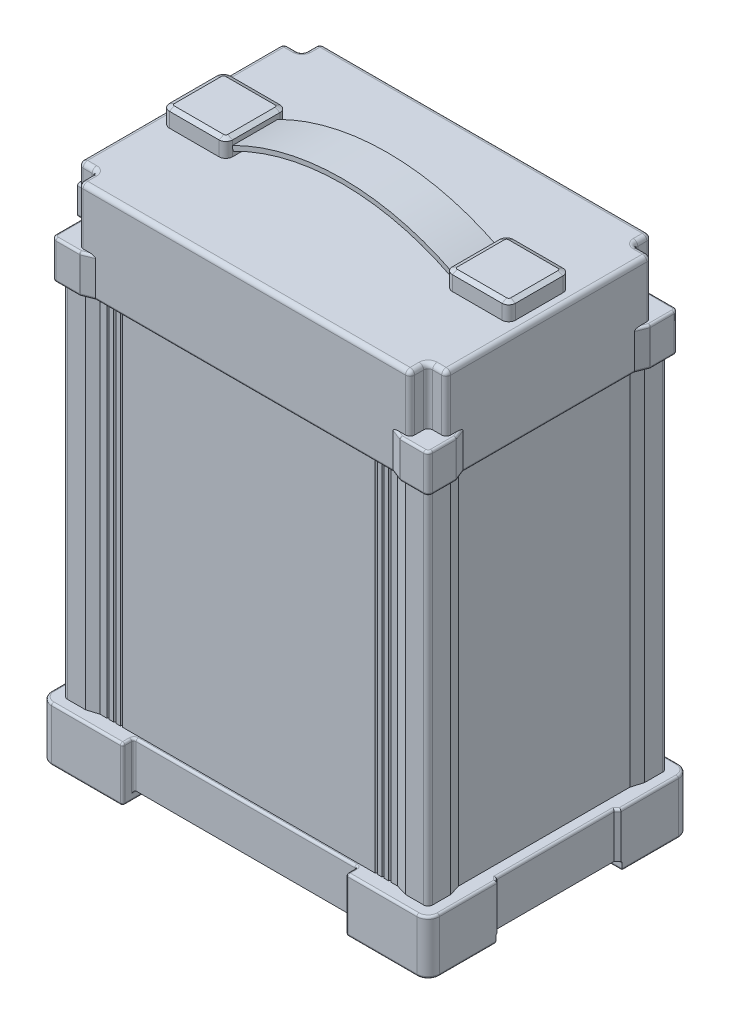
SolidWorks part; units mm, degrees
ref_plane "Front Plane" through (0, 0, 0) normal (0, 0, 1) x (1, 0, 0)
ref_plane "Top Plane" through (0, 0, 0) normal (0, 1, 0) x (1, 0, 0)
ref_plane "Right Plane" through (0, 0, 0) normal (1, 0, 0) x (0, 0, -1)
sketch "Sketch1" plane through (0, 0, 0) normal (0, 1, 0) x (1, 0, 0)
  line L0 (-81, 43) -> (-79.5, 38)
  line L1 (-81, -53) -> (-71, -53)
  line L2 (-81, -53) -> (-81, -43)
  line L3 (-81, 53) -> (-71, 53)
  line L4 (81, -53) -> (81, -43)
  line L6 (-79.5, 38) -> (-79.5, -38)
  line L7 (-66, -51.5) -> (66, -51.5)
  line L8 (79.5, 38) -> (79.5, -38)
  line L9 (-71, 53) -> (-66, 51.5)
  line L10 (-81, -43) -> (-79.5, -38)
  line L11 (-71, -53) -> (-66, -51.5)
  line L12 (66, 51.5) -> (71, 53)
  line L13 (81, 43) -> (79.5, 38)
  line L14 (81, -43) -> (79.5, -38)
  line L15 (71, -53) -> (66, -51.5)
  line L16 (71, 53) -> (81, 53)
  line L17 (71, -53) -> (81, -53)
  line L18 (81, 43) -> (81, 53)
  line L19 (-81, 43) -> (-81, 53)
  line L22 (-66, 51.5) -> (66, 51.5)
  line L23 (-79.5, 0) -> (79.5, 0) construction
  line L24 (0, 51.5) -> (0, -51.5) construction
  point P34 (0, 0)
  point P35 (0, 0)
  dimension "D1" = 162
  dimension "D2" = 106
  dimension "D5" = 10
  dimension "D6" = 5
  dimension "D7" = 10
  dimension "D8" = 1.5
  dimension "D4" = 10
  dimension "D9" = 10
  dimension "D3" = 1.5
extrude "Boss-Extrude1" add sketch "Sketch1" along normal blind 178
sketch "Sketch5" plane through (0, 0, 0) normal (0, -1, 0) x (1, 0, 0)
  line L0 (-66, 51.5) -> (66, 51.5) construction
  line L1 (0, 0) -> (0, 50000) construction
  line L2 (0, 0) -> (50000, 0) construction
  circle A0 centre (-62.5, 51.5) radius 0.5
  circle A1 centre (-59.5, 51.5) radius 0.5
  circle A2 centre (-56.5, 51.5) radius 0.5
  circle A3 centre (56.5, 51.5) radius 0.5
  circle A4 centre (59.5, 51.5) radius 0.5
  circle A5 centre (62.5, 51.5) radius 0.5
  circle A6 centre (62.5, -51.5) radius 0.5
  circle A7 centre (59.5, -51.5) radius 0.5
  circle A8 centre (56.5, -51.5) radius 0.5
  circle A9 centre (-56.5, -51.5) radius 0.5
  circle A10 centre (-59.5, -51.5) radius 0.5
  circle A11 centre (-62.5, -51.5) radius 0.5
  dimension "D1" = 1
  dimension "D2" = 3
  dimension "D3" = 3
  dimension "D4" = 3.5
extrude "Cut-Extrude1" cut sketch "Sketch5" against normal through all
fillet "Fillet1" radius 2 4 edges at (-81, 89, 53) (81, 89, 53) (-81, 89, -53) (81, 89, -53)
sketch "Sketch3" plane through (0, 0, 0) normal (0, 1, 0) x (1, 0, 0)
  line L1 (-86, 58) -> (-49.5, 58)
  line L2 (-86, 58) -> (-86, 28)
  line L3 (-86, -58) -> (-49.5, -58)
  line L4 (-49.5, 58) -> (-49.5, -58)
  line L5 (0, 0) -> (0, 89.5421) construction
  line L7 (-86, 28) -> (-84.5, 28)
  line L9 (-86, -28) -> (-84.5, -28)
  line L10 (-84.5, 28) -> (-84.5, -28)
  line L11 (-86, -28) -> (-86, -58)
  line L12 (86, 58) -> (86, 28)
  line L13 (-49.5, 53) -> (49.5, 53)
  line L14 (-49.5, 53) -> (-49.5, -53)
  line L15 (-49.5, -53) -> (49.5, -53)
  line L16 (49.5, 53) -> (49.5, -53)
  line L17 (86, 58) -> (49.5, 58)
  line L18 (49.5, 58) -> (49.5, -58)
  line L19 (86, -58) -> (49.5, -58)
  line L20 (86, -28) -> (86, -58)
  line L21 (86, -28) -> (84.5, -28)
  line L22 (84.5, 28) -> (84.5, -28)
  line L23 (86, 28) -> (84.5, 28)
  line L24 (66, 51.5) -> (63, 51.5) construction
  line L25 (-71, 53) -> (-79, 53) construction
  line L26 (-81, 51) -> (-81, 43) construction
  point P4 (-49.5, 0)
  point P14 (-84.5, 0)
  point P20 (49.5, 0)
  point P21 (0, 53)
  dimension "D3" = 1.5
  dimension "D4" = 30
  dimension "D5" = 1.5
  dimension "D1" = 5
  dimension "D2" = 5
  dimension "D6" = 99
extrude "Boss-Extrude2" add sketch "Sketch3" along normal blind 18 and the other way blind 2 separate body contours L9 L11 L3 L4 L1 L2 L7 L10 | L15 L5 L13 L4 | L5 L15 L16 L13 | L23 L12 L17 L18 L16 L19 L20 L21 L22 region at (-67.3958, 0, 0) region at (-24.75, 0, -51.5496) region at (67.3958, 0, 0)
sketch "Sketch4" plane through (0, -2, 0) normal (0, -1, 0) x (1, 0, 0)
  line L0 (-86, -28) -> (-84.5, -28) construction
  line L1 (-86, 58) -> (-49.5, 58)
  line L2 (-86, 58) -> (-86, 28)
  line L3 (-86, 28) -> (-49.5, 28)
  line L4 (-49.5, 58) -> (-49.5, 28)
  line L5 (-86, -58) -> (-49.5, -58)
  line L6 (-86, -58) -> (-86, -28)
  line L7 (-86, -28) -> (-49.5, -28)
  line L8 (-49.5, -58) -> (-49.5, -28)
  line L9 (86, 58) -> (49.5, 58) construction
  line L10 (86, -58) -> (49.5, -58)
  line L11 (86, -58) -> (86, -28)
  line L12 (86, -28) -> (49.5, -28)
  line L13 (49.5, -58) -> (49.5, -28)
  line L14 (86, 58) -> (49.5, 58)
  line L15 (86, 58) -> (86, 28)
  line L16 (86, 28) -> (49.5, 28)
  line L17 (49.5, 58) -> (49.5, 28)
extrude "Boss-Extrude3" add sketch "Sketch4" along normal blind 4
chamfer "Chamfer1" distance 2 angle 45 4 edges at (-84.5, 8, -28) (-84.5, 8, 28) (84.5, 8, 28) (84.5, 8, -28)
fillet "Fillet2" radius 1 56 edges at (67.75, -6, 28) (49.5, -6, 43) (67.75, -6, 58) (86, -6, 43) (-67.75, -6, 58) (-49.5, -6, 43) (-67.75, -6, 28) (-86, -6, 43) (-67.75, -6, -28) (-49.5, -6, -43) (-67.75, -6, -58) (-86, -6, -43) (67.75, -6, -58) (49.5, -6, -43) (67.75, -6, -28) (86, -6, -43) (-85.25, 18, -26.75) (-86, 18, -42.75) (-67.75, 18, -58) (-49.5, 18, -55.5) (0, 18, -53) (49.5, 18, 55.5) (67.75, 18, -58) (86, 18, -42.75) (85.25, 18, -26.75) (84.5, 18, 0) (85.25, 18, 26.75) (86, 18, 42.75) (67.75, 18, 58) (49.5, 18, -55.5) (0, 18, 53) (-49.5, 18, 55.5) (-67.75, 18, 58) (-86, 18, 42.75) (-85.25, 18, 26.75) (-84.5, 18, 0) (49.5, 6, -58) (49.5, 6, 58) (-49.5, 6, 58) (-49.5, 6, -58) (-67.75, -2, -28) (67.75, -2, -28) (67.75, -2, 28) (-67.75, -2, 28) (-49.5, -4, -28) (-49.5, -2, -40.5) (-49.5, 8, -53) (49.5, -2, 40.5) (49.5, -4, -28) (49.5, 8, -53) (49.5, -4, 28) (49.5, -2, -40.5) (49.5, 8, 53) (-49.5, -2, 40.5) (-49.5, -4, 28) (-49.5, 8, 53)
fillet "Fillet3" radius 5 12 edges at (85.7071, 17.7071, 57.7071) (85.7071, -5.7071, 57.7071) (85.7071, 17.7071, -57.7071) (85.7071, -5.7071, -57.7071) (-85.7071, 17.7071, -57.7071) (-85.7071, -5.7071, -57.7071) (-85.7071, 17.7071, 57.7071) (-85.7071, -5.7071, 57.7071) (-86, 6, 58) (-86, 6, -58) (86, 6, -58) (86, 6, 58)
sketch "Sketch6" plane through (0, 178, 0) normal (0, 1, 0) x (1, 0, 0)
  line L0 (-71, 55.5) -> (-66, 53.5)
  line L1 (-66, 53.5) -> (66, 53.5)
  line L2 (-81.5, 38) -> (-81.5, -38)
  line L5 (-83.5, 55.5) -> (-71, 55.5)
  line L6 (-83.5, 55.5) -> (-83.5, 43)
  line L9 (-83.5, 43) -> (-81.5, 38)
  line L10 (0, 0) -> (0, 142.5005) construction
  line L11 (0, 0) -> (234.2629, 0) construction
  line L13 (56, 51.5) -> (-56, 51.5) construction
  line L16 (-71, 53) -> (-79, 53) construction
  line L17 (-81, 51) -> (-81, 43) construction
  line L18 (83.5, 43) -> (81.5, 38)
  line L19 (83.5, 55.5) -> (83.5, 43)
  line L20 (83.5, 55.5) -> (71, 55.5)
  line L21 (81.5, 38) -> (81.5, -38)
  line L22 (71, 55.5) -> (66, 53.5)
  line L23 (71, -55.5) -> (66, -53.5)
  line L24 (83.5, -55.5) -> (71, -55.5)
  line L25 (83.5, -55.5) -> (83.5, -43)
  line L26 (83.5, -43) -> (81.5, -38)
  line L27 (-83.5, -43) -> (-81.5, -38)
  line L28 (-83.5, -55.5) -> (-83.5, -43)
  line L29 (-83.5, -55.5) -> (-71, -55.5)
  line L30 (-66, -53.5) -> (66, -53.5)
  line L31 (-71, -55.5) -> (-66, -53.5)
  point P20 (-75, 53)
  point P40 (0, 53.5)
  point P43 (81.5, 0)
  point P49 (-81.5, 0)
  point P50 (0, -53.5)
  dimension "D1" = 2.5
  dimension "D2" = 2.5
  dimension "D3" = 2
extrude "Boss-Extrude4" add sketch "Sketch6" along normal blind 42 separate body
sketch "Sketch7" plane through (0, 220, 0) normal (0, 1, 0) x (1, 0, 0)
  line L0 (-66, 53.5) -> (-73.5, 53.5)
  line L1 (-81.5, 45.5) -> (-81.5, 38)
  line L2 (-66, 53.5) -> (-71, 55.5)
  line L3 (-71, 55.5) -> (-83.5, 55.5)
  line L4 (-83.5, 55.5) -> (-83.5, 43)
  line L5 (-83.5, 55.5) -> (-83.5, 43) construction
  line L6 (-83.5, 43) -> (-81.5, 38)
  line L7 (0, 0) -> (0, 50000) construction
  line L10 (-81.5, 45.5) -> (-73.5, 45.5)
  line L11 (-73.5, 53.5) -> (-73.5, 45.5)
  line L12 (0, 0) -> (50000, 0) construction
  line L13 (73.5, 53.5) -> (73.5, 45.5)
  line L14 (81.5, 45.5) -> (73.5, 45.5)
  line L15 (83.5, 43) -> (81.5, 38)
  line L16 (83.5, 55.5) -> (83.5, 43)
  line L17 (71, 55.5) -> (83.5, 55.5)
  line L18 (66, 53.5) -> (71, 55.5)
  line L19 (81.5, 45.5) -> (81.5, 38)
  line L20 (66, 53.5) -> (73.5, 53.5)
  line L21 (66, -53.5) -> (73.5, -53.5)
  line L22 (81.5, -45.5) -> (81.5, -38)
  line L23 (66, -53.5) -> (71, -55.5)
  line L24 (71, -55.5) -> (83.5, -55.5)
  line L25 (83.5, -55.5) -> (83.5, -43)
  line L26 (83.5, -43) -> (81.5, -38)
  line L27 (81.5, -45.5) -> (73.5, -45.5)
  line L28 (73.5, -53.5) -> (73.5, -45.5)
  line L29 (-73.5, -53.5) -> (-73.5, -45.5)
  line L30 (-81.5, -45.5) -> (-73.5, -45.5)
  line L31 (-83.5, -43) -> (-81.5, -38)
  line L32 (-83.5, -55.5) -> (-83.5, -43)
  line L33 (-71, -55.5) -> (-83.5, -55.5)
  line L34 (-66, -53.5) -> (-71, -55.5)
  line L35 (-81.5, -45.5) -> (-81.5, -38)
  line L36 (-66, -53.5) -> (-73.5, -53.5)
  dimension "D1" = 8
  dimension "D2" = 8
extrude "Cut-Extrude2" cut sketch "Sketch7" against normal blind 25
fillet "Fillet4" radius 1 24 edges at (-68.5, 195, -54.5) (-71, 186.5, -55.5) (-77.25, 195, -55.5) (-83.5, 195, -49.25) (-83.5, 186.5, -43) (-82.5, 195, -40.5) (-83.5, 186.5, 43) (-83.5, 195, 49.25) (-82.5, 195, 40.5) (-77.25, 195, 55.5) (-68.5, 195, 54.5) (-71, 186.5, 55.5) (68.5, 195, 54.5) (77.25, 195, 55.5) (71, 186.5, 55.5) (83.5, 186.5, 43) (83.5, 195, 49.25) (82.5, 195, 40.5) (83.5, 186.5, -43) (71, 186.5, -55.5) (82.5, 195, -40.5) (83.5, 195, -49.25) (77.25, 195, -55.5) (68.5, 195, -54.5)
fillet "Fillet5" radius 2 32 edges at (-83.2071, 194.7071, 55.2071) (83.2071, 194.7071, 55.2071) (83.2071, 194.7071, -55.2071) (-83.2071, 194.7071, -55.2071) (-77.5, 220, 45.5) (-81.5, 220, 0) (-77.5, 220, -45.5) (-73.5, 220, -49.5) (0, 220, -53.5) (73.5, 220, -49.5) (77.5, 220, -45.5) (81.5, 220, 0) (77.5, 220, 45.5) (73.5, 220, 49.5) (0, 220, 53.5) (-73.5, 220, 49.5) (-83.5, 186, -55.5) (-81.5, 207.5, -45.5) (-73.5, 207.5, -53.5) (-73.5, 207.5, -45.5) (73.5, 207.5, -53.5) (73.5, 207.5, -45.5) (81.5, 207.5, -45.5) (83.5, 186, -55.5) (83.5, 186, 55.5) (81.5, 207.5, 45.5) (73.5, 207.5, 53.5) (73.5, 207.5, 45.5) (-73.5, 207.5, 53.5) (-73.5, 207.5, 45.5) (-81.5, 207.5, 45.5) (-83.5, 186, 55.5)
fillet "Fillet6" radius 1 32 edges at (-83.482, 178, -43.0035) (-82.4642, 178, -40.4106) (-81.5, 178, 0) (-82.4642, 178, 40.4106) (-83.482, 178, 43.0035) (-83.5, 178, 48.3463) (-82.9142, 178, 54.9142) (-76.3463, 178, 55.5) (-71.0035, 178, 55.482) (-68.4106, 178, 54.4642) (0, 178, 53.5) (68.4106, 178, 54.4642) (71.0035, 178, 55.482) (76.3463, 178, 55.5) (82.9142, 178, 54.9142) (83.5, 178, 48.3463) (83.482, 178, 43.0035) (82.4642, 178, 40.4106) (81.5, 178, 0) (82.4642, 178, -40.4106) (83.482, 178, -43.0035) (83.5, 178, -48.3463) (82.9142, 178, -54.9142) (76.3463, 178, -55.5) (71.0035, 178, -55.482) (68.4106, 178, -54.4642) (0, 178, -53.5) (-68.4106, 178, -54.4642) (-71.0035, 178, -55.482) (-76.3463, 178, -55.5) (-82.9142, 178, -54.9142) (-83.5, 178, -48.3463)
sketch "Sketch9" plane through (0, 220, 0) normal (0, 1, 0) x (1, 0, 0)
  line L0 (79.5, -43.5) -> (79.5, 43.5) construction
  line L1 (76.75, 14) -> (48.75, 14)
  line L2 (76.75, 14) -> (76.75, -13)
  line L3 (76.75, -13) -> (48.75, -13)
  line L4 (48.75, 14) -> (48.75, -13)
  line L5 (71.5, -53.5) -> (-71.5, -53.5) construction
  dimension "D1" = 27
  dimension "D2" = 28
  dimension "D3" = 2.75
  dimension "D4" = 40.5
extrude "Boss-Extrude6" add sketch "Sketch9" along normal blind 7.5
fillet "Fillet7" radius 3 4 edges at (48.75, 223.75, 13) (76.75, 223.75, 13) (48.75, 223.75, -14) (76.75, 223.75, -14)
chamfer "Chamfer2" distance 1 angle 65 8 edges at (49.6287, 227.5, -13.1213) (62.75, 227.5, -14) (75.8713, 227.5, -13.1213) (76.75, 227.5, -0.5) (75.8713, 227.5, 12.1213) (62.75, 227.5, 13) (49.6287, 227.5, 12.1213) (48.75, 227.5, -0.5) first distance on face at (49.9393, 223.75, -12.8107) first distance on face at (62.75, 223.75, -14) first distance on face at (75.5607, 223.75, -12.8107) first distance on face at (76.75, 223.75, -0.5) first distance on face at (75.5607, 223.75, 11.8107) first distance on face at (62.75, 223.75, 13) first distance on face at (49.9393, 223.75, 11.8107) first distance on face at (48.75, 223.75, -0.5)
mirror "Mirror1" about plane through (0, 0, 0) normal (1, 0, 0) of "Fillet7", "Chamfer2", "Boss-Extrude6"
sketch "Sketch10" plane through (0, 0, 0) normal (0, 0, 1) x (1, 0, 0)
  line L0 (48.75, 226.5) -> (48.75, 220) construction
  line L1 (-48.75, 220) -> (-48.75, 226.5) construction
  line L2 (71.5, 220) -> (-71.5, 220) construction
  arc A0 (48.75, 223.25) -> (-48.75, 223.25) centre (0, 127.9947) ccw
  point P3 (0, 235)
  dimension "D1" = 15
extrude "Extrude-Thin1" add sketch "Sketch10" along normal mid plane 20 separate body thin thin type mid plane wall 2
sketch "Sketch11" plane through (-81.5, 0, 0) normal (-1, 0, 0) x (0, 0, 1)
  line L1 (43.5, 209) -> (16.5, 209)
  line L2 (43.5, 209) -> (43.5, 196)
  line L3 (43.5, 196) -> (16.5, 196)
  line L4 (16.5, 209) -> (16.5, 196)
  line L5 (-43.5, 220) -> (43.5, 220) construction
  line L6 (53.5, 218) -> (53.5, 195) construction
  point P6 (16.5, 202.5)
  point P7 (30, 209)
  dimension "D1" = 17.5
  dimension "D2" = 23.5
  dimension "D3" = 27
  dimension "D4" = 13
extrude "Boss-Extrude7" add sketch "Sketch11" along normal blind 2.5 separate body
fillet "Fillet8" radius 1 4 edges at (-82.75, 196, 16.5) (-82.75, 209, 16.5) (-82.75, 196, 43.5) (-82.75, 209, 43.5)
equation "\"D7@Sketch1\"=\"D5@Sketch1\""
equation "\"D8@Sketch1\"=\"D3@Sketch1\""
equation "\"D4@Sketch1\"=\"D5@Sketch1\""
equation "\"D9@Sketch1\"=\"D5@Sketch1\""
equation "\"D2@Sketch3\"=\"D1@Sketch3\""
equation "\"D3@Sketch5\"=\"D2@Sketch5\""
equation "\"D2@Sketch6\"=\"D1@Sketch6\""
equation "\"D2@Sketch7\"=\"D1@Sketch7\""
